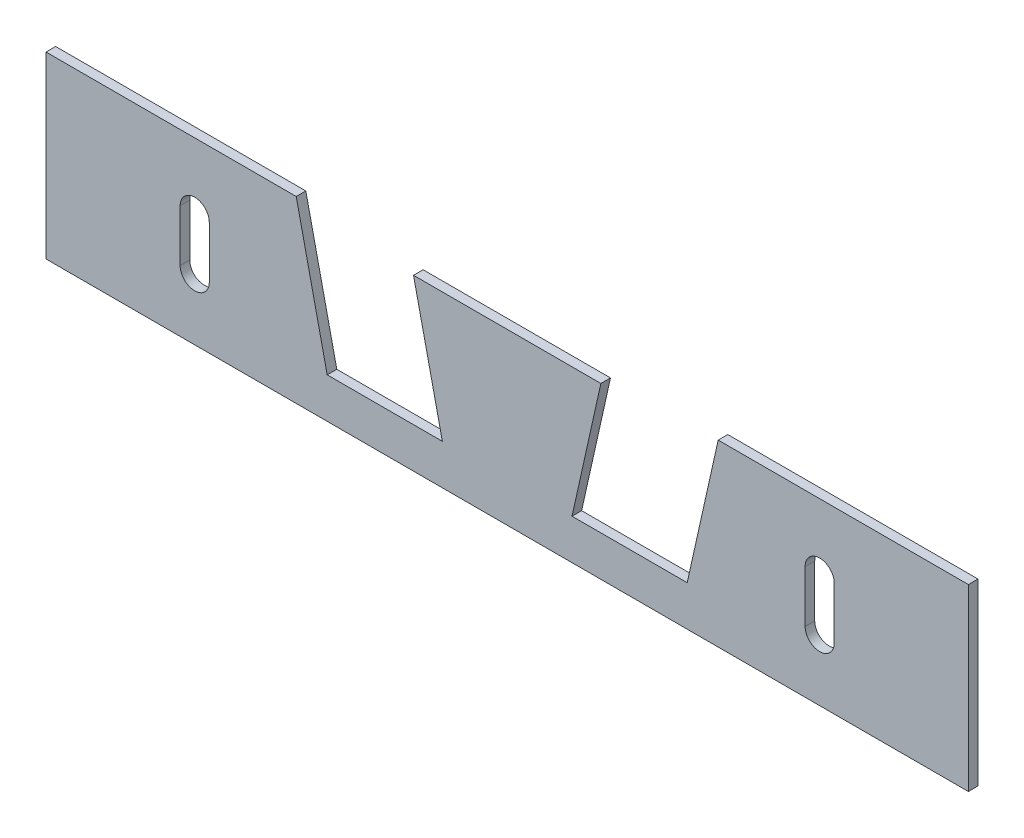
SolidWorks part; units mm, degrees
ref_plane "Спереди" through (0, 0, 0) normal (0, 0, 1) x (1, 0, 0)
ref_plane "Сверху" through (0, 0, 0) normal (0, 1, 0) x (1, 0, 0)
ref_plane "Справа" through (0, 0, 0) normal (1, 0, 0) x (0, 0, -1)
sketch "Эскиз1" plane through (0, 0, 0) normal (0, 0, 1) x (1, 0, 0)
  line L0 (-19.9097, -34.7962) -> (-16.9078, -48.261)
  line L5 (-48, -34.7962) -> (-19.9097, -34.7962)
  line L6 (-48, -34.7962) -> (-48, -53.4542)
  line L7 (-48, -53.4542) -> (48, -53.4542)
  line L8 (48, -34.7962) -> (48, -53.4542)
  line L9 (-16.9078, -48.261) -> (-7.9953, -48.261)
  line L10 (-7.9953, -48.261) -> (-10.9972, -34.7962)
  line L11 (-10.9972, -34.7962) -> (10.9972, -34.7962)
  line L12 (10.9972, -34.7962) -> (7.9953, -48.261)
  line L13 (7.9953, -48.261) -> (16.9078, -48.261)
  line L14 (16.9078, -48.261) -> (19.9097, -34.7962)
  line L15 (19.9097, -34.7962) -> (48, -34.7962)
  line L16 (-10.9972, -34.7962) -> (10.9972, -34.7962)
  circle A0 centre (32.5214, -44.3645) radius 1.5
  circle A1 centre (-32.5214, -44.3645) radius 1.5
extrude "Бобышка-Вытянуть1" add sketch "Эскиз1" along normal blind 1 contours L15 L14 L13 L12 L11 L10 L9 L0 L5 L6 L7 L8 A1 A0 region at (0, -44.5285, 0)
sketch "Эскиз2" plane through (0, 0, 1) normal (0, 0, 1) x (1, 0, 0)
  line L0 (-32.5214, -47.0664) -> (-32.5214, -41.6627) construction
  line L1 (-34.0371, -47.0664) -> (-34.0371, -41.6627)
  line L2 (-31.0058, -47.0664) -> (-31.0058, -41.6627)
  line L3 (0, -53.4542) -> (0, -30.1683) construction
  line L4 (-48, -53.4542) -> (48, -53.4542) construction
  line L5 (32.5214, -47.0664) -> (32.5214, -41.6627) construction
  line L6 (34.0371, -47.0664) -> (34.0371, -41.6627)
  line L7 (31.0058, -47.0664) -> (31.0058, -41.6627)
  arc A0 (-34.0371, -47.0664) -> (-31.0058, -47.0664) centre (-32.5214, -47.0664) ccw
  arc A1 (-31.0058, -41.6627) -> (-34.0371, -41.6627) centre (-32.5214, -41.6627) ccw
  arc A2 (34.0371, -47.0664) -> (31.0058, -47.0664) centre (32.5214, -47.0664) cw
  arc A3 (31.0058, -41.6627) -> (34.0371, -41.6627) centre (32.5214, -41.6627) cw
  point P2 (-32.5214, -44.3645)
  point P15 (32.5214, -44.3645)
extrude "Вырез-Вытянуть1" cut sketch "Эскиз2" against normal blind 10
sketch "Эскиз3" plane through (0, 0, 1) normal (0, 0, 1) x (1, 0, 0)
  line L0 (-21.9588, -34.7962) -> (-18.7339, -49.261)
  line L1 (-48, -34.7962) -> (-19.9097, -34.7962) construction
  line L2 (-18.7339, -49.261) -> (-6.7478, -49.261)
  line L3 (-6.7478, -49.261) -> (-9.7497, -35.7962)
  line L4 (-9.7497, -35.7962) -> (9.7497, -35.7962)
  line L5 (9.7497, -35.7962) -> (6.7474, -49.2628)
  line L6 (6.7474, -49.2628) -> (18.7335, -49.2628)
  line L7 (18.7335, -49.2628) -> (21.9588, -34.7962)
  line L20 (48, -34.7962) -> (19.9097, -34.7962)
  line L21 (19.9097, -34.7962) -> (16.9078, -48.261)
  line L22 (16.9078, -48.261) -> (7.9953, -48.261)
  line L23 (7.9953, -48.261) -> (10.9972, -34.7962)
  line L24 (10.9972, -34.7962) -> (-10.9972, -34.7962)
  line L25 (-10.9972, -34.7962) -> (-7.9953, -48.261)
  line L26 (-7.9953, -48.261) -> (-16.9078, -48.261)
  line L27 (-16.9078, -48.261) -> (-19.9097, -34.7962)
  line L28 (-19.9097, -34.7962) -> (-48, -34.7962)
  line L29 (-48, -34.7962) -> (-48, -53.4542)
  line L30 (-48, -53.4542) -> (48, -53.4542)
  line L31 (48, -53.4542) -> (48, -34.7962)
  line L32 (21.9588, -34.7962) -> (19.9097, -34.7962)
  line L33 (19.9097, -34.7962) -> (16.9078, -48.261)
  line L34 (16.9078, -48.261) -> (7.9953, -48.261)
  line L35 (7.9953, -48.261) -> (10.9972, -34.7962)
  line L36 (10.9972, -34.7962) -> (-10.9972, -34.7962)
  line L37 (-10.9972, -34.7962) -> (-7.9953, -48.261)
  line L38 (-7.9953, -48.261) -> (-16.9078, -48.261)
  line L39 (-16.9078, -48.261) -> (-19.9097, -34.7962)
  line L40 (-19.9097, -34.7962) -> (-21.9588, -34.7962)
  dimension "D2" = 180
  dimension "D3" = 1
  dimension "D4" = 2
  dimension "D6" = 1
  dimension "D7" = 1
  dimension "D8" = 1
  dimension "D9" = 1.0018
  dimension "D10" = 2
  dimension "D1" = 0
extrude "Вырез-Вытянуть2" cut sketch "Эскиз3" against normal blind 10
